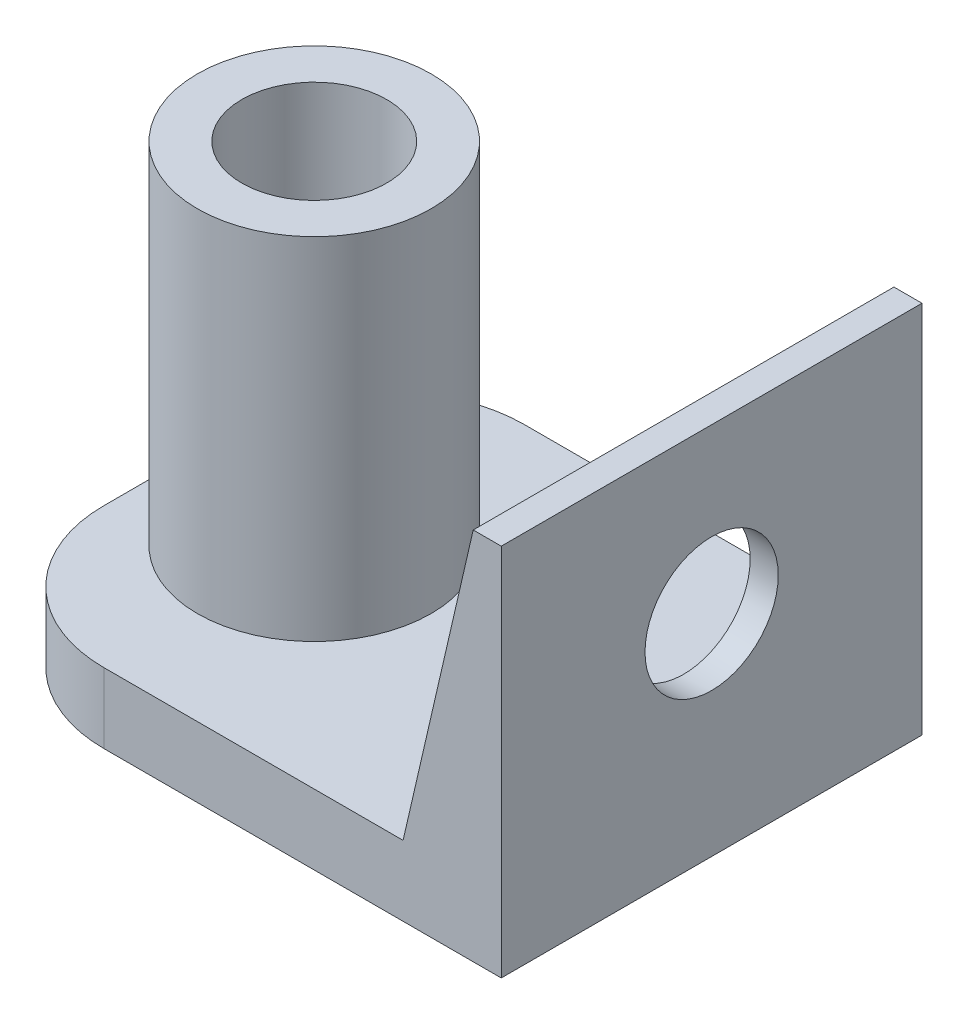
SolidWorks part; units mm, degrees
ref_plane "Front" through (0, 0, 0) normal (0, 0, 1) x (1, 0, 0)
ref_plane "Top" through (0, 0, 0) normal (0, 1, 0) x (1, 0, 0)
ref_plane "Right" through (0, 0, 0) normal (1, 0, 0) x (0, 0, -1)
sketch "Esquisse1" plane through (0, 0, 0) normal (0, 0, 1) x (1, 0, 0)
  line L0 (0, 0) -> (23, 0)
  line L1 (23, 0) -> (23, 16)
  line L2 (23, 16) -> (21.8, 16)
  line L3 (21.8, 16) -> (21.8, 3)
  line L4 (21.8, 3) -> (0, 3)
  line L5 (0, 3) -> (0, 0)
  dimension "D1" = 23
  dimension "D2" = 1.2
  dimension "D3" = 16
  dimension "D4" = 3
extrude "Boss.-Extru.1" add sketch "Esquisse1" along normal blind 18
sketch "Esquisse2" plane through (23, 0, 0) normal (1, 0, 0) x (0, 0, -1)
  line L0 (-9, 16) -> (-9, 0) construction
  line L1 (-18, 16) -> (0, 16) construction
  line L2 (-18, 0) -> (0, 0) construction
  circle A0 centre (-9, 9) radius 2.85
  dimension "D1" = 5.7
  dimension "D2" = 7
extrude "Enlèv. mat.-Extru.1" cut sketch "Esquisse2" against normal through all both and the other way through all
sketch "Esquisse3" plane through (0, 0, 0) normal (0, -1, 0) x (1, 0, 0)
  line L0 (0, 9) -> (6, 9) construction
  line L1 (0, 18) -> (0, 0) construction
  line L2 (23, 18) -> (23, 0) construction
  circle A0 centre (6, 9) radius 2.7
  dimension "D1" = 5.4
  dimension "D2" = 17
extrude "Enlèv. mat.-Extru.2" cut sketch "Esquisse3" against normal through all both and the other way through all
sketch "Esquisse4" plane through (0, 0, 18) normal (0, 0, 1) x (1, 0, 0)
  line L0 (21.8, 3) -> (21.8, 16)
  line L1 (21.8, 16) -> (21.8, 3) construction
  line L2 (21.8, 16) -> (18.8, 3)
  line L3 (21.8, 3) -> (0, 3) construction
  line L4 (18.8, 3) -> (21.8, 3)
  dimension "D1" = 3
extrude "Boss.-Extru.2" add sketch "Esquisse4" against normal blind 3
extrude "Boss.-Extru.3" add sketch "Esquisse4<2>" along normal blind 3 from vertex starting at point (21.8, 16, 0)
sketch "Esquisse4<2>" plane through (0, 0, 18) normal (0, 0, 1) x (1, 0, 0) same geometry as "Esquisse4"
fillet "Congé1" radius 6 2 edges at (0, 1.5, 0) (0, 1.5, 18)
sketch "Esquisse5" plane through (0, 3, 0) normal (0, 1, 0) x (1, 0, 0)
  circle A0 centre (6, -9) radius 14
  dimension "D1" = 28
sketch "Esquisse6" plane through (0, 3, 0) normal (0, 1, 0) x (1, 0, 0)
  circle A0 centre (6, -9) radius 3.1
  circle A3 centre (6, -9) radius 5
  dimension "D1" = 6.2
  dimension "D2" = 10
extrude "Boss.-Extru.4" add sketch "Esquisse6" along normal blind 15
sketch "Esquisse7" plane through (0, 3, 0) normal (0, 1, 0) x (1, 0, 0)
  circle A0 centre (6, -9) radius 2.7
  circle A1 centre (6, -9) radius 3.1
  circle A2 centre (6, -9) radius 2.7 construction
  circle A3 centre (6, -9) radius 3.1 construction
extrude "Boss.-Extru.5" add sketch "Esquisse7" along normal blind 7
